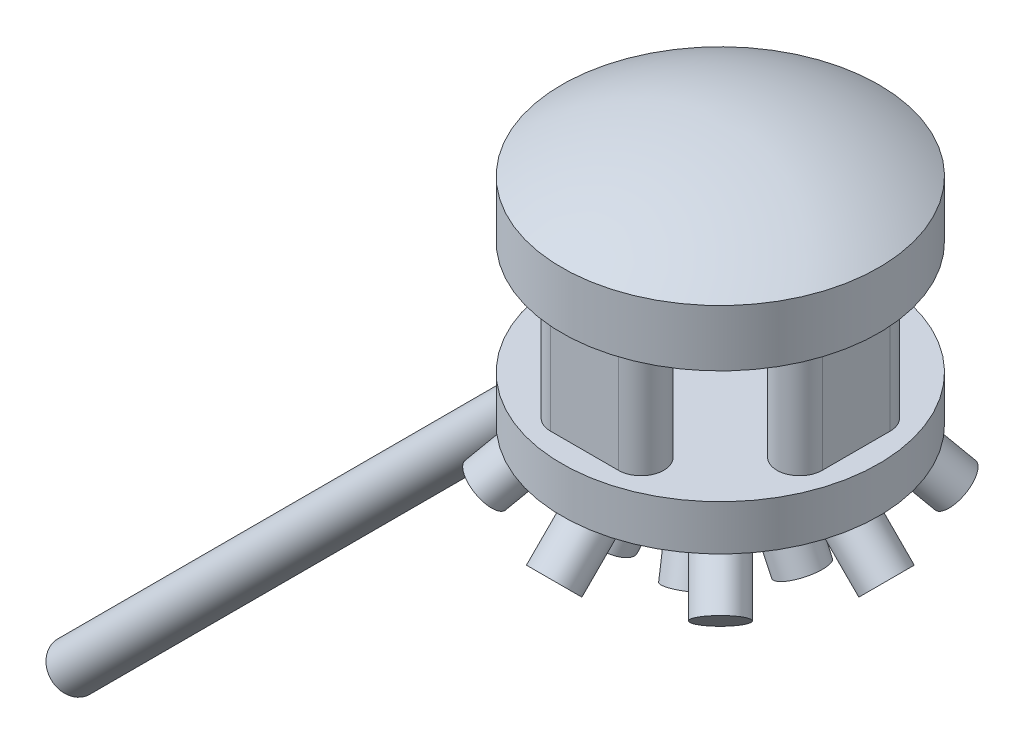
SolidWorks part; units mm, degrees
ref_plane "Front Plane" through (0, 0, 0) normal (0, 0, 1) x (1, 0, 0)
ref_plane "Top Plane" through (0, 0, 0) normal (0, 1, 0) x (1, 0, 0)
ref_plane "Right Plane" through (0, 0, 0) normal (1, 0, 0) x (0, 0, -1)
sketch "Sketch1" plane through (0, 0, 0) normal (0, 0, 1) x (1, 0, 0)
  line L0 (0, 0) -> (0, 3.175)
  line L1 (0, 3.175) -> (-8.89, 3.175)
  line L2 (-8.89, 3.175) -> (-8.89, 0)
  line L3 (-8.89, 0) -> (0, 0)
  dimension "D1" = 3.175
  dimension "D2" = 8.89
revolve "button top" add sketch "Sketch1" angle 360 about L0
dome "domey top" faces to dome 1 distance 2.54 reverse direction no elliptical dome no face at (0, 3.175, -8.89) parameters "D1"=2.54
ref_axis "button central axis" through (0, 3.175, 0) along (0, -1, 0)
sketch "Sketch2" plane through (0, 0, 0) normal (0, -1, 0) x (1, 0, 0)
  line L0 (-1.905, -6.35) -> (1.905, -6.35) construction
  line L1 (-1.905, -5.08) -> (1.905, -5.08)
  line L2 (-1.905, -7.62) -> (1.905, -7.62)
  arc A0 (-1.905, -5.08) -> (-1.905, -7.62) centre (-1.905, -6.35) ccw
  arc A1 (1.905, -7.62) -> (1.905, -5.08) centre (1.905, -6.35) ccw
  point P2 (0, -6.35)
  dimension "D3" = 1.27
  dimension "D1" = 6.35
  dimension "D2" = 3.81
extrude "one leg" add sketch "Sketch2" along normal blind 6.35
pattern_circular "all legs" count 4 over 360 about axis through (0, 3.175, 0) along (0, -1, 0) of "one leg"
sketch "Sketch3" plane through (0, -6.35, 0) normal (0, -1, 0) x (1, 0, 0)
  circle A0 centre (0, 0) radius 8.89
  dimension "D1" = 17.78
extrude "base" add sketch "Sketch3" along normal blind 2.54
sketch "Sketch5" plane through (0, -6.35, 0) normal (0, 1, 0) x (1, 0, 0)
  circle A0 centre (0, 0) radius 1.27
  dimension "D1" = 2.54
sketch "Sketch6" plane through (0, 0, 0) normal (1, 0, 0) x (0, 0, -1)
  line L0 (0, -8.89) -> (0, -11.938)
  line L1 (-8.89, -8.89) -> (8.89, -8.89) construction
  line L2 (0, -8.89) -> (8.89, -8.89)
  spline S0 degree 3 poles (0, -11.938) (2.9633, -11.938) (6.4782, -10.4523) (8.89, -8.89) knots 0 0 0 0 1 1 1 1
revolve "Revolve2" add sketch "Sketch6" angle 360 about L0
ref_plane "nubplane-right" through (6.985, -6.985, 0) normal (-0.7071, 0.7071, 0) x (0, 0, -1)
sketch "Sketch7" plane through (6.985, -6.985, 0) normal (-0.7071, 0.7071, 0) x (0, 0, -1)
  circle A0 centre (0, 1.778) radius 1.27
  dimension "D2" = 2.54
  dimension "D1" = 1.778
extrude "Boss-Extrude1" add sketch "Sketch7" against normal blind 5.08
pattern_circular "CirPattern1" count 8 over 360 about axis through (0, 3.175, 0) along (0, -1, 0) of "Boss-Extrude1"
ref_plane "nubplane-smaller" through (3.3395, -7.1616, 0) normal (-0.4226, 0.9063, 0) x (0, 0, -1)
sketch "Sketch8" plane through (3.3395, -7.1616, 0) normal (-0.4226, 0.9063, 0) x (0, 0, -1)
  circle A0 centre (0, 1.5908) radius 1.27
extrude "Boss-Extrude2" add sketch "Sketch8" against normal blind 6.35
pattern_circular "CirPattern2" count 6 over 360 about axis through (0, 3.175, 0) along (0, -1, 0) of "Boss-Extrude2"
extrude "Boss-Extrude3" add sketch "Sketch5" against normal blind 7.62
sketch "Sketch9" plane through (-10.5771, -10.5771, 0) normal (-0.7071, -0.7071, 0) x (0, 0, 1)
  circle A0 centre (0, -1.778) radius 1.27
extrude "Boss-Extrude4" add sketch "Sketch9" along normal blind 38.1
